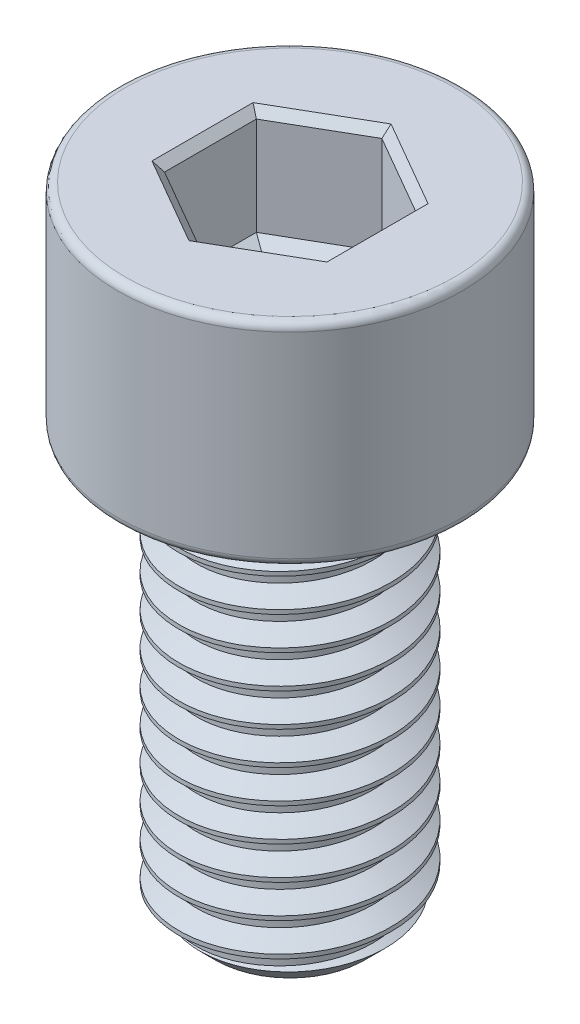
SolidWorks part; units mm, degrees
material "AISI Type A2 Tool Steel"
ref_plane "Front Plane" through (0, 0, 0) normal (0, 0, 1) x (1, 0, 0)
ref_plane "Top Plane" through (0, 0, 0) normal (0, 1, 0) x (1, 0, 0)
ref_plane "Right Plane" through (0, 0, 0) normal (1, 0, 0) x (0, 0, -1)
sketch "Sketch1" plane through (0, 0, 0) normal (0, 1, 0) x (1, 0, 0)
  circle A0 centre (0, 0) radius 4
  dimension "D1" = 8
extrude "Boss-Extrude1" add sketch "Sketch1" along normal blind 16
thread "Thread1" pitch 1.25 method cut profile "Thread Profile1" start angle 0, offset 1.25, length 0, pitch 1.25, diameter 8
ref_plane "Plane1" through (-4, 17.25, 0) normal (0, 0, 1) x (-1, 0, 0)
sketch "Thread Profile1" plane through (-4, 17.25, 0) normal (0, 0, 1) x (-1, 0, 0)
  line L0 (0, 0) -> (0, 1.25) construction
  line L11 (0, 0) -> (0, 1.0937)
  line L12 (0, 1.0937) -> (-0.6766, 0.7031)
  line L13 (-0.6766, 0.7031) -> (-0.6766, 0.3906)
  line L15 (-0.6766, 0.3906) -> (0, 0)
  line L17 (-0.6766, 0.5469) -> (0, 0.5469) construction
  point P2 (0, 0)
  dimension "Pitch" = 1.25
  dimension "Profile_Angle" = 60
  dimension "Profile_Land" = 0.3125
  dimension "Profile_Height" = 0.6766
sketch "Sketch2" plane through (0, 16, 0) normal (0, 1, 0) x (1, 0, 0)
  circle A0 centre (0, 0) radius 6.5
  dimension "D1" = 13
extrude "Boss-Extrude2" add sketch "Sketch2" along normal blind 8
sketch "Sketch5" plane through (0, 0, 0) normal (0, 0, 1) x (1, 0, 0)
  line L0 (0, 0) -> (0, 0.9986) construction
  line L1 (0, 0) -> (4.01, 0) construction
  line L2 (4.01, 0) -> (4.01, 1.2)
  line L3 (4.01, 1.2) -> (2.81, 0)
  line L4 (2.81, 0) -> (4.01, 0)
  dimension "D1" = 1.2
  dimension "D2" = 45
  dimension "D3" = 4.01
revolve "Cut-Revolve1" cut sketch "Sketch5" angle 360 about L0
fillet "Fillet1" radius 0.3 2 edges at (0, 24, 6.5) (0, 16, 6.5)
sketch "Sketch6" plane through (0, 24, 0) normal (0, 1, 0) x (1, 0, 0)
  line L1 (0, 3.4641) -> (-3, 1.7321)
  line L2 (-3, 1.7321) -> (-3, -1.7321)
  line L3 (-3, -1.7321) -> (0, -3.4641)
  line L4 (0, -3.4641) -> (3, -1.7321)
  line L5 (3, -1.7321) -> (3, 1.7321)
  line L6 (3, 1.7321) -> (0, 3.4641)
  circle A0 centre (0, 0) radius 3 construction
  dimension "D1" = 6
extrude "Cut-Extrude1" cut sketch "Sketch6" against normal blind 4
chamfer "Chamfer1" distance 0.3 angle 45 6 edges at (-3, 24, 0) (-1.5, 24, 2.5981) (1.5, 24, 2.5981) (3, 24, 0) (1.5, 24, -2.5981) (-1.5, 24, -2.5981)
sketch "Sketch7" plane through (0, 20, 0) normal (0, 1, 0) x (1, 0, 0)
  line L1 (0, 3.4641) -> (-3, 1.7321)
  line L2 (-3, 1.7321) -> (-3, -1.7321)
  line L3 (-3, -1.7321) -> (0, -3.4641)
  line L4 (0, -3.4641) -> (3, -1.7321)
  line L5 (3, -1.7321) -> (3, 1.7321)
  line L6 (3, 1.7321) -> (0, 3.4641)
  circle A0 centre (0, 0) radius 3 construction
extrude "Cut-Extrude2" cut sketch "Sketch7" against normal blind 0.4 draft 60
